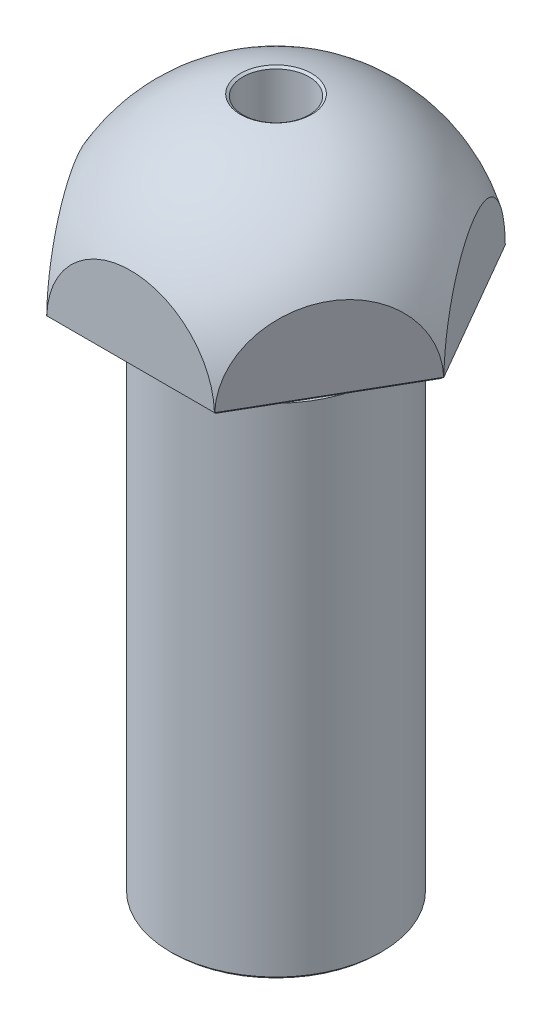
SolidWorks part; units mm, degrees
material "AISI 304"
ref_plane "Front" through (0, 0, 0) normal (0, 0, 1) x (1, 0, 0)
ref_plane "Top" through (0, 0, 0) normal (0, 1, 0) x (1, 0, 0)
ref_plane "Right" through (0, 0, 0) normal (1, 0, 0) x (0, 0, -1)
sketch "Sketch2" plane through (0, 0, 0) normal (0, 1, 0) x (1, 0, 0)
  line L1 (-6.3509, 11) -> (-12.7017, 0)
  line L2 (-12.7017, 0) -> (-6.3509, -11)
  line L3 (-6.3509, -11) -> (6.3509, -11)
  line L4 (6.3509, -11) -> (12.7017, 0)
  line L5 (12.7017, 0) -> (6.3509, 11)
  line L6 (6.3509, 11) -> (-6.3509, 11)
  circle A0 centre (0, 0) radius 11 construction
  circle A1 centre (0, 0) radius 19.2608
  dimension "D2" = 38.5215
  dimension "D1" = 22
sketch "Sketch3" plane through (0, 0, 0) normal (0, 0, 1) x (1, 0, 0)
  line L0 (0, 0) -> (8, 0)
  line L1 (50, 0) -> (-50, 0) construction
  line L2 (8, 0) -> (8, 38)
  line L3 (8, 40) -> (12.7, 40)
  line L4 (0, -50) -> (0, 50) construction
  line L5 (0, 0) -> (0, 52.7)
  line L6 (0, 0) -> (0, 47.1852) construction
  arc A0 (12.7, 40) -> (0, 52.7) centre (0, 40) ccw
  arc A1 (8, 40) -> (8, 38) centre (8, 39) ccw
  dimension "D3" = 47.1852
  dimension "D5" = 1
  dimension "D6" = 12.7
  dimension "D1" = 8
  dimension "D2" = 40
revolve "Revolve1" add sketch "Sketch3" angle 360 about L6
extrude "Cut-Extrude1" cut sketch "Sketch2" along normal blind 50
hole_wizard "M6x1.0 Tapped Hole1" positions "Sketch5" profile "Sketch4" tap size "M6x1.0" standard "ANSI Metric" end condition through all
sketch "Sketch5" plane through (0, 0, 0) normal (0, -1, 0) x (-1, 0, 0)
  point P0 (0, 0)
cosmetic thread "Hole Thread1" parameters "D2"=6
sketch "Sketch4" plane through (0, 0, 0) normal (1, 0, 0) x (0, 0, -1)
  line L0 (0, 0) -> (0, 52.7)
  line L1 (0, 52.7) -> (2.5, 52.7)
  line L2 (2.5, 52.7) -> (2.5, 0)
  line L5 (2.5, 0) -> (0, 0)
  line L11 (0, -6.35) -> (0, 107.95) construction
  dimension "Thru Tap Drill Dia." = 5
  dimension "Thru Tap Drill Depth" = 52.7
chamfer "Chamfer1" distance 0.2 angle 45 9 edges at (9.5263, 40, -5.5) (9.5263, 40, 5.5) (0, 40, 11) (-9.5263, 40, 5.5) (-9.5263, 40, -5.5) (0, 40, -11) (0, 38, -8) (0, 0, -8) (0, 52.4515, -2.5) first distance on face at (0, 40, 0) first distance on face at (0, 40, -8) first distance on face at (0, 38, -8) first distance on face at (0, 52.4515, -2.5)
sketch "Sketch6" plane through (0, 0, 0) normal (0, -1, 0) x (1, 0, 0)
  circle A0 centre (0, 0) radius 2.5
extrude "Boss-Extrude1" add sketch "Sketch6" against normal blind 27
